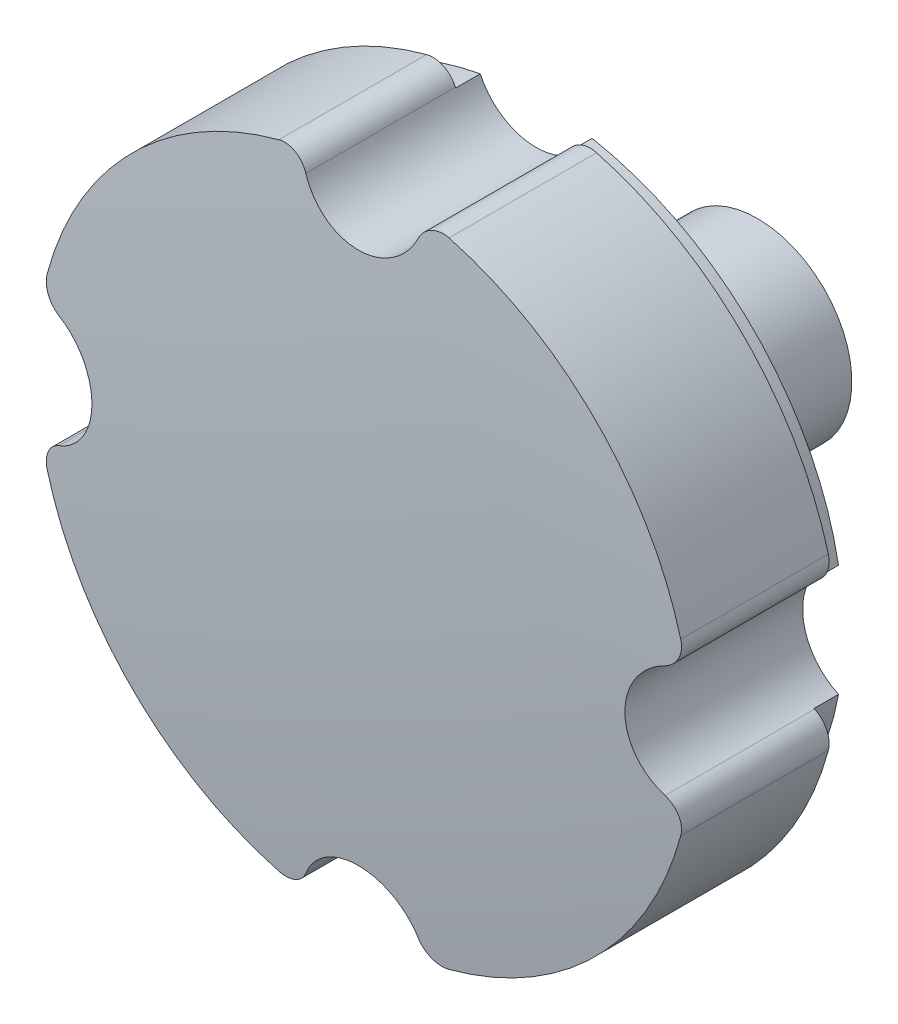
SolidWorks part; units mm, degrees
ref_plane "Front Plane" through (0, 0, 0) normal (0, 0, 1) x (1, 0, 0)
ref_plane "Top Plane" through (0, 0, 0) normal (0, 1, 0) x (1, 0, 0)
ref_plane "Right Plane" through (0, 0, 0) normal (1, 0, 0) x (0, 0, -1)
sketch "Sketch1" plane through (0, 0, 0) normal (0, 1, 0) x (1, 0, 0)
  line L0 (0, 358.8435) -> (0, -36.4755) construction
  line L1 (0, 20.005) -> (0, 0)
  line L2 (-40, 2.005) -> (-40, 20.005)
  line L3 (-40, 20.005) -> (-37.5, 20.005)
  line L4 (-37.5, 20.005) -> (-37.5, 23.005)
  line L5 (-37.5, 23.005) -> (-11.5, 23.005)
  line L6 (-11.5, 23.005) -> (-11.5, 50.005)
  line L7 (-11.5, 50.005) -> (-6, 50.005)
  line L8 (-6, 50.005) -> (-6, 20.005)
  line L9 (-6, 20.005) -> (0, 20.005)
  arc A1 (-40, 2.005) -> (0, 0) centre (0, 400) ccw
  dimension "D9" = 800
  dimension "D1" = 30
  dimension "D2" = 18
  dimension "D3" = 3
  dimension "D4" = 80
  dimension "D5" = 23
  dimension "D6" = 12
  dimension "D7" = 75
  dimension "D8" = 30
revolve "Revolve1" add sketch "Sketch1" angle 360 about L0
sketch "Sketch2" plane through (0, 0, 0) normal (0, 0, 1) x (1, 0, 0)
  circle A0 centre (0, 0) radius 40 construction
  circle A1 centre (0, 40) radius 7.5
  circle A2 centre (0, 0) radius 40 construction
  circle A3 centre (40, 0) radius 7.5
  circle A4 centre (0, 0) radius 40 construction
  circle A5 centre (0, -40) radius 7.5
  circle A6 centre (0, 0) radius 40 construction
  circle A7 centre (-40, 0) radius 7.5
  point P17 (0, 0)
  dimension "D1" = 80
  dimension "D2" = 15
  dimension "D3" = 4
extrude "Cut-Extrude1" cut sketch "Sketch2" against normal up to next
ref_plane "Plane1" through (0, 0, -20.005) normal (0, 0, -1) x (-1, 0, 0)
sketch "Sketch3" plane through (0, 0, -20.005) normal (0, 0, -1) x (-1, 0, 0)
  line L0 (0, 0) -> (-57.745, 57.745) construction
  line L1 (0, 0) -> (-62.0039, 0) construction
  dimension "D1" = 45
fillet "Fillet1" radius 3 8 edges at (-39.2969, 7.467, -11.005) (-39.2969, -7.467, -11.005) (-7.467, -39.2969, -11.005) (7.467, -39.2969, -11.005) (39.2969, -7.467, -11.005) (39.2969, 7.467, -11.005) (7.467, 39.2969, -11.005) (-7.467, 39.2969, -11.005)
sketch "Sketch4" plane through (0, 0, 0) normal (0, 1, 0) x (1, 0, 0)
  line L0 (0, 68.9802) -> (0, -14.4472) construction
sketch "Sketch5" plane through (0, 0, 0) normal (0, 0, 1) x (1, 0, 0)
  line L0 (0, 0) -> (-33.6671, 33.6671) construction
